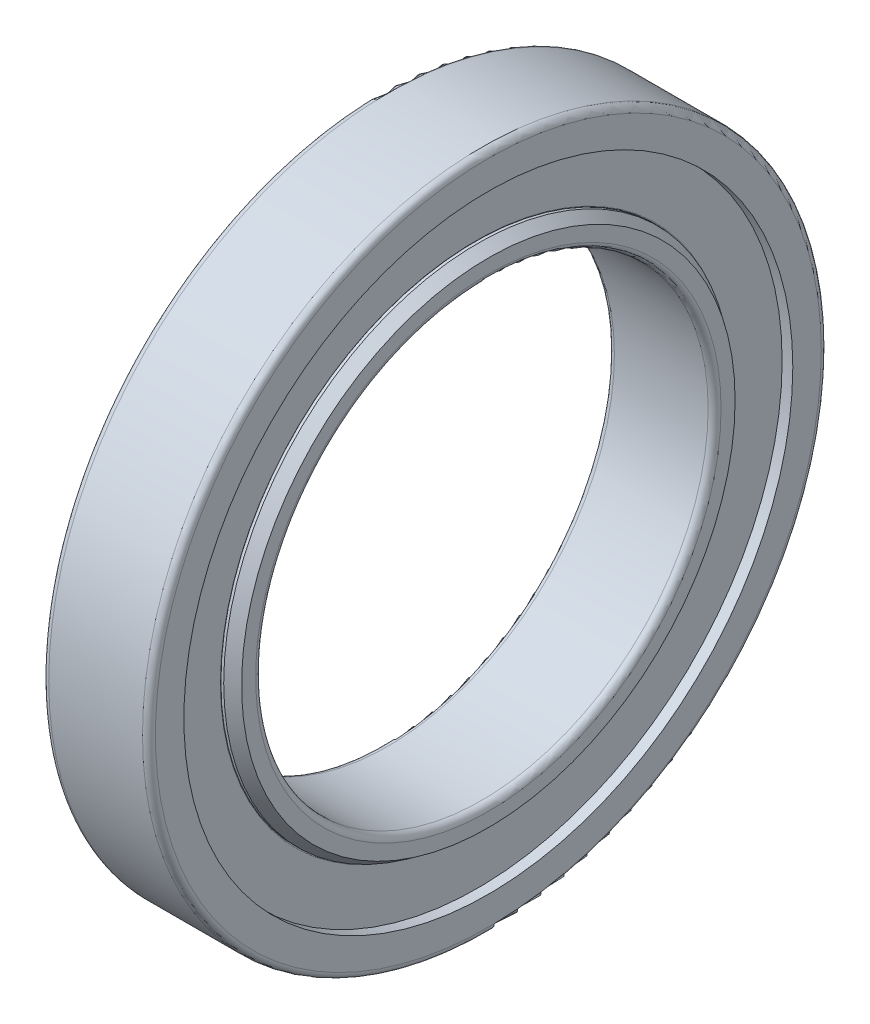
SolidWorks part; units mm, degrees
material "201 Annealed Stainless Steel (SS)"
ref_plane "Plane1" through (0, 0, 0) normal (0, 0, 1) x (1, 0, 0)
ref_plane "Plane2" through (0, 0, 0) normal (0, 1, 0) x (1, 0, 0)
ref_plane "Plane3" through (0, 0, 0) normal (1, 0, 0) x (0, 0, -1)
sketch "Clipboard" plane through (0, 0, 0) normal (0, 0, 1) x (1, 0, 0)
  line L0 (-10, 0) -> (10, 0) construction
  line L1 (0, 0) -> (157.0543, -5.4845)
  line L2 (0, 0) -> (87.4467, 3.0537)
  line L3 (0, 0) -> (192.7325, -6.7304)
  line L4 (0, 0) -> (-22.3573, -0.3902)
sketch "OutRacSke" plane through (0, 0, 0) normal (0, 0, 1) x (1, 0, 0)
  line L0 (-13.2, 94.1938) -> (-16.5, 94.1938)
  line L1 (-16.5, 94.1938) -> (-16.5, 103)
  line L2 (-14.5, 105) -> (14.5, 105)
  line L3 (16.5, 103) -> (16.5, 94.1938)
  line L4 (16.5, 94.1938) -> (13.2, 94.1938)
  line L5 (13.2, 94.1938) -> (13.2, 96.425)
  line L6 (13.2, 96.425) -> (-13.2, 96.425)
  line L7 (-13.2, 96.425) -> (-13.2, 94.1938)
  line L8 (-90, 0) -> (90, 0) construction
  arc A0 (-16.5, 103) -> (-14.5, 105) centre (-14.5, 103) cw
  arc A1 (14.5, 105) -> (16.5, 103) centre (14.5, 103) cw
revolve "OuterRace" add sketch "OutRacSke" angle 360 about L8 reverse direction yes
sketch "RolDetSke" plane through (0, 0, 0) normal (0, 0, 1) x (1, 0, 0)
  line L0 (-12.54, 96.0728) -> (-12.54, 87.5)
  line L1 (-12.54, 87.5) -> (12.54, 87.5)
  line L2 (12.54, 87.5) -> (12.54, 96.0728)
  line L3 (12.1828, 96.43) -> (-12.1828, 96.43)
  line L4 (-33.6, 87.5) -> (33.6, 87.5) construction
  arc A0 (12.54, 96.0728) -> (12.1828, 96.43) centre (12.1828, 96.0728) ccw
  arc A1 (-12.1828, 96.43) -> (-12.54, 96.0728) centre (-12.1828, 96.0728) ccw
revolve "RollerDetailed" [suppressed] add sketch "RolDetSke" angle 360 about L4 reverse direction yes
ref_axis "Axis1" through (-50, 0, 0) along (1, 0, 0)
sketch "RolSimSke" plane through (0, 101.6, 0) normal (0, 0, 1) x (1, 0, 0)
  line L0 (-12.54, -5.5272) -> (-12.54, -22.6728)
  line L1 (25.4, -101.6) -> (-25.4, -101.6) construction
  line L2 (12.54, -22.6728) -> (12.54, -5.5272)
  line L3 (12.1828, -5.17) -> (-12.1828, -5.17)
  line L5 (12.1828, -23.03) -> (-12.1828, -23.03)
  arc A0 (12.54, -5.5272) -> (12.1828, -5.17) centre (12.1828, -5.5272) ccw
  arc A1 (-12.1828, -5.17) -> (-12.54, -5.5272) centre (-12.1828, -5.5272) ccw
  arc A2 (12.54, -22.6728) -> (12.1828, -23.03) centre (12.1828, -22.6728) cw
  arc A3 (-12.1828, -23.03) -> (-12.54, -22.6728) centre (-12.1828, -22.6728) cw
revolve "RollersSimplified" add sketch "RolSimSke" angle 360 about L1
sketch "InsRacSke" plane through (0, 0, 0) normal (0, 0, 1) x (1, 0, 0)
  line L0 (-13.2, 78.575) -> (-16.5, 76.3438)
  line L1 (-16.5, 76.3438) -> (-16.5, 72)
  line L2 (-14.5, 70) -> (14.5, 70)
  line L3 (16.5, 72) -> (16.5, 76.3437)
  line L4 (16.5, 76.3437) -> (13.2, 78.575)
  line L5 (13.2, 78.575) -> (-13.2, 78.575)
  line L6 (-90, 0) -> (90, 0) construction
  line L7 (0, 0) -> (0, 177.8) construction
  arc A0 (-16.5, 72) -> (-14.5, 70) centre (-14.5, 72) ccw
  arc A1 (14.5, 70) -> (16.5, 72) centre (14.5, 72) ccw
revolve "InnerRace" add sketch "InsRacSke" angle 360 about L6 reverse direction yes
pattern_circular "RollersDetailed" [suppressed] count 2 every 180 about axis through (-50, 0, 0) along (1, 0, 0)
sketch "CagSpiSke" plane through (0, 0, 0) normal (0, 0, 1) x (1, 0, 0)
  line L0 (14.85, 85.2675) -> (14.85, 89.7325)
  line L1 (14.85, 89.7325) -> (-14.85, 89.7325)
  line L2 (-14.85, 89.7325) -> (-14.85, 85.2675)
  line L3 (-14.85, 85.2675) -> (14.85, 85.2675)
  line L4 (-90, 0) -> (90, 0) construction
revolve "CageSpine" [suppressed] add sketch "CagSpiSke" angle 0.001 about L4
equation "\"CLdia@Clipboard\" =  ( \"Race_OD@Clipboard\" + \"Race_ID@Clipboard\" )  / 4"
equation "\"Race_OD@OutRacSke\" = \"Race_OD@Clipboard\""
equation "\"halfCylLen@OutRacSke\" = \"Cyl_Len@OutRacSke\" / 2"
equation "\"RolCLRad@RolDetSke\" = \"CLdia@Clipboard\""
equation "\"Roller_diameter@RolDetSke\" =  ( \"Race_OD@Clipboard\" - \"Race_ID@Clipboard\" )  / 2 + .01"
equation "\"Roller_diameter@RolSimSke\" =  ( \"Race_OD@Clipboard\" - \"Race_ID@Clipboard\" )  / 2 + .01"
equation "\"radius@RolDetSke\" = \"Roller_diameter@RolDetSke\" / 50"
equation "\"Length@RolDetSke\" = \"Cyl_Len@OutRacSke\" * .95"
equation "\"halfLength@RolDetSke\" = \"Length@RolDetSke\" / 2"
equation "\"thickness@CagSpiSke\"  = \"Roller_diameter@RolDetSke\" * .25"
equation "\"Cag_IR@CagSpiSke\" =  \"RolCLRad@RolDetSke\" * 2 - \"thickness@CagSpiSke\""
equation "\"Rol_Length@RolSimSke\" = \"Cyl_Len@InsRacSke\" * .95"
equation "\"halfLength@RolSimSke\" = \"Rol_Length@RolSimSke\" / 2"
equation "\"radius@RolSimSke\" = \"radius@RolDetSke\""
equation "\"D1@RolSimSke\" = \"CLdia@Clipboard\" -  ( \"Roller_diameter@RolSimSke\" / 2 ) "
equation "\"Max_count@Clipboard\" = int( 3.14159265 / atn(( \"Roller_diameter@RolDetSke\" / 2) / sqr( \"RolCLRad@RolDetSke\"  *  \"RolCLRad@RolDetSke\" - ( \"Roller_diameter@RolDetSke\" / 2) *  ( \"Roller_diameter@RolDetSke\" / 2))))"
equation "\"Max_count@Clipboard\" = ((sgn( \"Max_count@Clipboard\" - \"Count@Clipboard\" )-1)*( \"Max_count@Clipboard\" - \"Count@Clipboard\" ))/-2+ \"Count@Clipboard\""
equation "\"Count@RollersDetailed\" = int( \"Show_count@Clipboard\" ) "
equation "\"Count@RollersDetailed\" = ((sgn( \"Count@RollersDetailed\" - \"Max_count@Clipboard\" )-1)*( \"Count@RollersDetailed\" - \"Max_count@Clipboard\" ))/-2+ \"Max_count@Clipboard\""
equation "\"Count@RollersDetailed\" = ((sgn( \"Count@RollersDetailed\" - \"Min_count@Clipboard\" )+1)*( \"Count@RollersDetailed\" - \"Min_count@Clipboard\"))/2 +\"Min_count@Clipboard\""
equation "\"Angle@RollersDetailed\" = 360.0 / \"Max_count@Clipboard\""
equation "\"radius@InsRacSke\" = \"radius@OutRacSke\""
equation "\"groove_dp@InsRacSke\" = \"groove_dp@OutRacSke\""
equation "\"Width@InsRacSke\" = \"Width@OutRacSke\""
equation "\"halfWidth@OutRacSke\" = \"Width@OutRacSke\" / 2"
equation "\"halfWidth@InsRacSke\" = \"Width@InsRacSke\" / 2"
equation "\"Race_ID@InsRacSke\" = \"Race_ID@Clipboard\""
equation "\"Cyl_Len@InsRacSke\" = \"Cyl_Len@OutRacSke\""
equation "\"Angle@CageSpine\" =  \"Angle@RollersDetailed\" * ( \"Count@RollersDetailed\" -1 + int( \"Count@RollersDetailed\" / \"Max_count@Clipboard\" ) )  + 0.001 -  int( \"Count@RollersDetailed\" / \"Max_count@Clipboard\" ) * 0.001"
equation "\"Angle@CageSpine\" =  \"Angle@CageSpine\" * int( \"Min_count@Clipboard\" / 2) + int(1 / \"Min_count@Clipboard\")  * 0.001"
equation "\"width@CagSpiSke\" =   ( \"Width@InsRacSke\" + \"Cyl_Len@InsRacSke\" )  / 2"
equation "\"halfwidth@CagSpiSke\" = \"width@CagSpiSke\" / 2"
